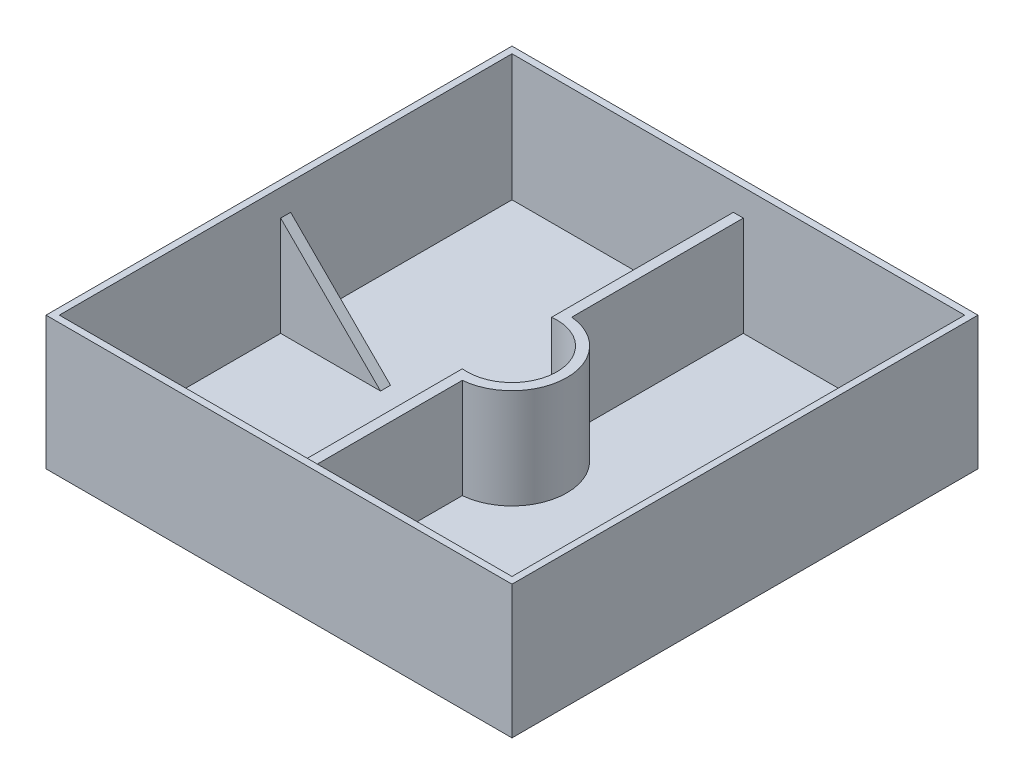
SolidWorks part; units mm, degrees
ref_plane "Front Plane" through (0, 0, 0) normal (0, 0, 1) x (1, 0, 0)
ref_plane "Top Plane" through (0, 0, 0) normal (0, 1, 0) x (1, 0, 0)
ref_plane "Right Plane" through (0, 0, 0) normal (1, 0, 0) x (0, 0, -1)
sketch "Sketch1" plane through (0, 0, 0) normal (0, 1, 0) x (1, 0, 0)
  line L1 (-88.9, -88.9) -> (88.9, -88.9)
  line L2 (-88.9, -88.9) -> (-88.9, 88.9)
  line L3 (-88.9, 88.9) -> (88.9, 88.9)
  line L4 (88.9, -88.9) -> (88.9, 88.9)
  line L5 (-88.9, -88.9) -> (88.9, 88.9) construction
  line L6 (-88.9, 88.9) -> (88.9, -88.9) construction
  point P0 (0, 0)
  dimension "D1" = 177.8
extrude "Boss-Extrude1" add sketch "Sketch1" along normal blind 50.8
shell "Shell1" thickness 2.54 removed face at (0, 50.8, 0)
sketch "Sketch2" plane through (0, 0, 0) normal (0, 0, 1) x (1, 0, 0)
  line L0 (-86.36, 40.64) -> (-48.26, 2.54)
  line L2 (-86.36, 50.8) -> (-86.36, 2.54) construction
  line L3 (86.36, 2.54) -> (-86.36, 2.54) construction
  point P2 (-86.36, 26.67)
  point P3 (0, 0)
  point P4 (0, 0)
  point P5 (-86.36, 26.67)
  point P6 (-86.36, 26.67)
  point P7 (0, 0)
  point P8 (0, 0)
  point P9 (-86.36, 30.3141)
  point P12 (-86.36, 31.085)
  point P13 (-56.657, 2.54)
  point P17 (0, 0)
  dimension "D1" = 38.1
  dimension "D2" = 45
rib "Rib2" sketch "Sketch2" sketch "Sketch2" thickness 3.81 extrusion direction parallel to sketch draft on no parameters "D1"=3.81
mirror "Mirror1" about plane through (0, 0, 0) normal (1, 0, 0) of "Rib2"
ref_plane "Plane1" through (0, 40.64, 0) normal (0, 1, 0) x (1, 0, 0)
sketch "Sketch3" plane through (0, 40.64, 0) normal (0, 1, 0) x (1, 0, 0)
  line L0 (0, 86.36) -> (0, -86.36) construction
  line L1 (86.36, 86.36) -> (-86.36, 86.36) construction
  line L2 (-86.36, -86.36) -> (86.36, -86.36) construction
  line L3 (0, 19.05) -> (0, 86.36)
  line L4 (0, -19.05) -> (0, -86.36)
  arc A0 (0, -19.05) -> (0, 19.05) centre (0, 0) ccw
  dimension "D1" = 19.05
rib "Rib3" sketch "Sketch3" sketch "Sketch3" thickness 3.81 extrusion direction normal to sketch draft on no parameters "D1"=3.81
